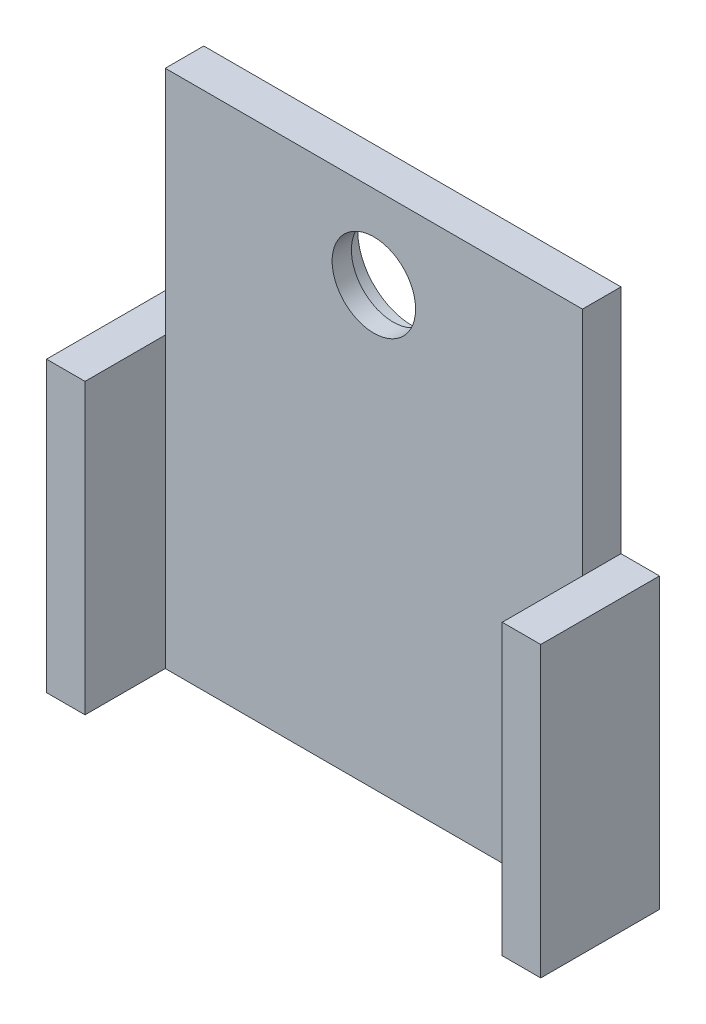
SolidWorks part; units mm, degrees
ref_plane "Plano frontal" through (0, 0, 0) normal (0, 0, 1) x (1, 0, 0)
ref_plane "Plano superior" through (0, 0, 0) normal (0, 1, 0) x (1, 0, 0)
ref_plane "Plano direito" through (0, 0, 0) normal (1, 0, 0) x (0, 0, -1)
other "Centro da massa"
sketch "Esboço1" plane through (0, 0, 0) normal (0, 0, 1) x (1, 0, 0)
  line L0 (16, -4.75) -> (16, -11.25) construction
  line L1 (16.25, -11.25) -> (-16.25, -11.25)
  line L2 (16.25, -11.25) -> (16.25, 29.25)
  line L3 (16.25, 29.25) -> (-16.25, 29.25)
  line L4 (-16.25, -11.25) -> (-16.25, 29.25)
  line L5 (-16, -11.25) -> (-16, -4.75) construction
  line L8 (-15, -11.25) -> (-10.25, -11.25) construction
  line L10 (-11, 29.25) -> (11, 29.25) construction
  dimension "D1" = 0.25
  dimension "D2" = 0.25
extrude "Ressalto-extrusão1" add sketch "Esboço1" against normal blind 3
sketch "Esboço4" plane through (-16.25, 0, 0) normal (-1, 0, 0) x (0, 0, 1)
  line L1 (-3, -11.25) -> (6.25, -11.25)
  line L2 (-3, -11.25) -> (-3, 11.25)
  line L3 (-3, 11.25) -> (6.25, 11.25)
  line L4 (6.25, -11.25) -> (6.25, 11.25)
  line L5 (6.5, -8.3463) -> (6.5, 13.8) construction
  line L6 (28.25, 11.25) -> (69.75, 11.25) construction
  dimension "D1" = 0.25
extrude "Ressalto-extrusão2" add sketch "Esboço4" along normal blind 3
mirror "Espelhar1" about plane through (0, 0, 0) normal (1, 0, 0) of "Ressalto-extrusão2"
sketch "Esboço5" plane through (0, 0, -3) normal (0, 0, -1) x (-1, 0, 0)
  circle A3 centre (0, 22.75) radius 4.25
  circle A4 centre (0, 22.75) radius 4 construction
  dimension "D1" = 0.25
extrude "Corte-extrusão1" cut sketch "Esboço5" against normal offset from surface (1.5 mm away) 1.5 up to face at (0, 9.75, 0)
sketch "Esboço6" plane through (0, 0, -3) normal (0, 0, -1) x (-1, 0, 0)
  circle A0 centre (0, 22.75) radius 3.25 construction
  circle A1 centre (0, 22.75) radius 3.25
extrude "Corte-extrusão2" cut sketch "Esboço6" against normal through all
